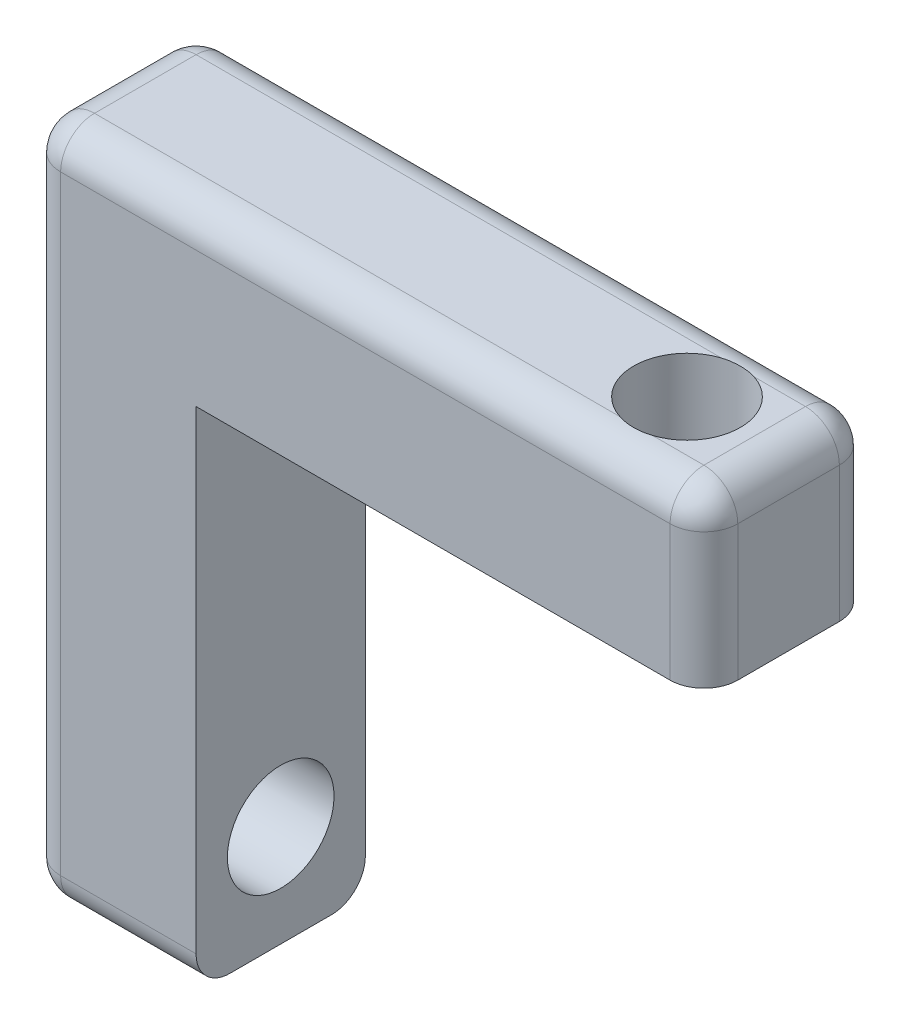
SolidWorks part; units mm, degrees
ref_plane "Front" through (0, 0, 0) normal (0, 0, 1) x (1, 0, 0)
ref_plane "Top" through (0, 0, 0) normal (0, 1, 0) x (1, 0, 0)
ref_plane "Right" through (0, 0, 0) normal (1, 0, 0) x (0, 0, -1)
sketch "Sketch1" plane through (0, 0, 0) normal (0, 0, 1) x (1, 0, 0)
  line L1 (0, 0) -> (6.35, 0)
  line L2 (0, 0) -> (0, 25.4)
  line L4 (6.35, 0) -> (6.35, 19.05)
  line L5 (0, 25.4) -> (25.4, 25.4)
  line L7 (6.35, 19.05) -> (25.4, 19.05)
  line L8 (25.4, 25.4) -> (25.4, 19.05)
  dimension "D1" = 25.4
  dimension "D2" = 6.35
extrude "Boss-Extrude1" add sketch "Sketch1" along normal blind 6.35
sketch "Sketch2" plane through (0, 25.4, 0) normal (0, 1, 0) x (1, 0, 0)
  line L0 (25.4, -6.35) -> (25.4, 0) construction
  circle A0 centre (21.59, -3.175) radius 2
  point P4 (25.4, -3.175)
  dimension "D1" = 4
  dimension "D2" = 3.81
extrude "Cut-Extrude1" cut sketch "Sketch2" against normal through all
sketch "Sketch3" plane through (0, 0, 0) normal (-1, 0, 0) x (0, 0, 1)
  line L0 (6.35, 0) -> (0, 0) construction
  circle A0 centre (3.175, 3.81) radius 2
  point P4 (3.175, 0)
  dimension "D1" = 4
  dimension "D2" = 3.81
extrude "Cut-Extrude2" cut sketch "Sketch3" against normal through all
fillet "Fillet1" radius 1.27 11 edges at (3.175, 0, 0) (3.175, 0, 6.35) (0, 0, 3.175) (0, 12.7, 0) (0, 12.7, 6.35) (12.7, 25.4, 0) (12.7, 25.4, 6.35) (25.4, 22.225, 0) (25.4, 22.225, 6.35) (25.4, 25.4, 3.175) (0, 25.4, 3.175)
